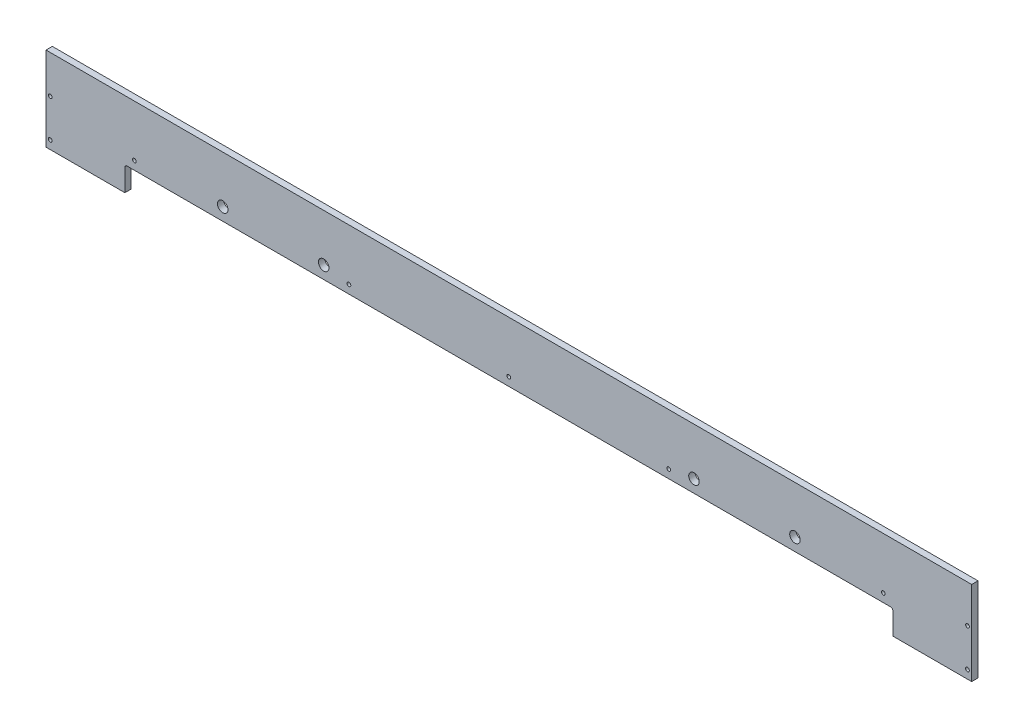
SolidWorks part; units mm, degrees
material "LEXAN (CLEAR)"
ref_plane "Front" through (0, 0, 0) normal (0, 0, 1) x (1, 0, 0)
ref_plane "Top" through (0, 0, 0) normal (0, 1, 0) x (1, 0, 0)
ref_plane "Right" through (0, 0, 0) normal (1, 0, 0) x (0, 0, -1)
ref_axis "Axis1" through (0, 50, 0) along (0, -1, 0)
sketch "Sketch1" plane through (0, 0, 0) normal (0, 0, 1) x (1, 0, 0)
  line L1 (-698.5, 63.5) -> (698.5, 63.5)
  line L2 (-698.5, 63.5) -> (-698.5, -63.5)
  line L3 (-698.5, -63.5) -> (698.5, -63.5)
  line L4 (698.5, 63.5) -> (698.5, -63.5)
  line L5 (-698.5, 63.5) -> (698.5, -63.5) construction
  line L6 (-698.5, -63.5) -> (698.5, 63.5) construction
  point P0 (0, 0)
  dimension "D1" = 1397
  dimension "D2" = 127
extrude "Boss-Extrude1" add sketch "Sketch1" against normal blind 9.525
sketch "Sketch2" plane through (0, 0, 0) normal (0, 0, 1) x (1, 0, 0)
  line L0 (-698.5, -63.5) -> (698.5, -63.5) construction
  line L1 (-579.4375, -63.5) -> (579.4375, -63.5)
  line L2 (-579.4375, -63.5) -> (-579.4375, -30.1625)
  line L3 (-576.2625, -26.9875) -> (576.2625, -26.9875)
  line L4 (579.4375, -63.5) -> (579.4375, -30.1625)
  line L5 (0, 0) -> (0, -63.5) construction
  arc A0 (576.2625, -26.9875) -> (579.4375, -30.1625) centre (576.2625, -30.1625) cw
  arc A1 (-579.4375, -30.1625) -> (-576.2625, -26.9875) centre (-576.2625, -30.1625) cw
  point P11 (579.4375, -26.9875)
  dimension "D2" = 3.175
  dimension "D1" = 36.5125
  dimension "D3" = 1158.875
extrude "Cut-Extrude1" cut sketch "Sketch2" against normal through all
hole_wizard "#10 Clearance Hole1" positions "Sketch4" profile "Sketch3" hole size "#10" standard "ANSI Inch" end condition up to next
sketch "Sketch4" plane through (0, 0, 0) normal (0, 0, 1) x (1, 0, 0)
  line L1 (698.5, -63.5) -> (698.5, 63.5) construction
  line L2 (-698.5, -63.5) -> (-579.4375, -63.5) construction
  line L3 (-698.5, 63.5) -> (-698.5, -63.5) construction
  point P2 (-692.15, 6.35)
  point P4 (-692.15, -50.8)
  point P8 (692.15, 6.35)
  point P10 (692.15, -50.8)
  point P24 (-565.15, -14.2875)
  point P26 (-241.3, -14.2875)
  point P28 (0, -14.2875)
  point P30 (241.3, -14.2875)
  point P32 (565.15, -14.2875)
  dimension "D1" = 6.35
  dimension "D2" = 6.35
  dimension "D3" = 12.7
  dimension "D4" = 69.85
  dimension "D5" = 49.2125
  dimension "D6" = 241.3
  dimension "D7" = 565.15
  dimension "D8" = 241.3
  dimension "D9" = 565.15
sketch "Sketch3" plane through (-692.15, 6.35, 0) normal (1, 0, 0) x (0, -1, 0)
  line L0 (0, 0) -> (0, 9.525)
  line L1 (0, 9.525) -> (2.8067, 9.525)
  line L2 (2.8067, 9.525) -> (2.8067, 0)
  line L5 (2.8067, 0) -> (0, 0)
  line L11 (0, -6.35) -> (0, 107.95) construction
  dimension "Thru Hole Dia." = 5.6134
  dimension "Thru Hole Depth" = 9.525
sketch "Sketch8" plane through (0, 0, 0) normal (0, 0, 1) x (1, 0, 0)
  line L0 (698.5, 63.5) -> (-698.5, 63.5) construction
  circle A0 centre (-431.8, -7.9375) radius 7.9375
  circle A1 centre (-279.4, -7.9375) radius 7.9375
  circle A2 centre (279.4, -7.9375) radius 7.9375
  circle A3 centre (431.8, -7.9375) radius 7.9375
  dimension "D1" = 15.875
  dimension "D2" = 152.4
  dimension "D3" = 152.4
  dimension "D4" = 279.4
  dimension "D5" = 279.4
  dimension "D6" = 71.4375
extrude "Cut-Extrude2" cut sketch "Sketch8" against normal up to next
